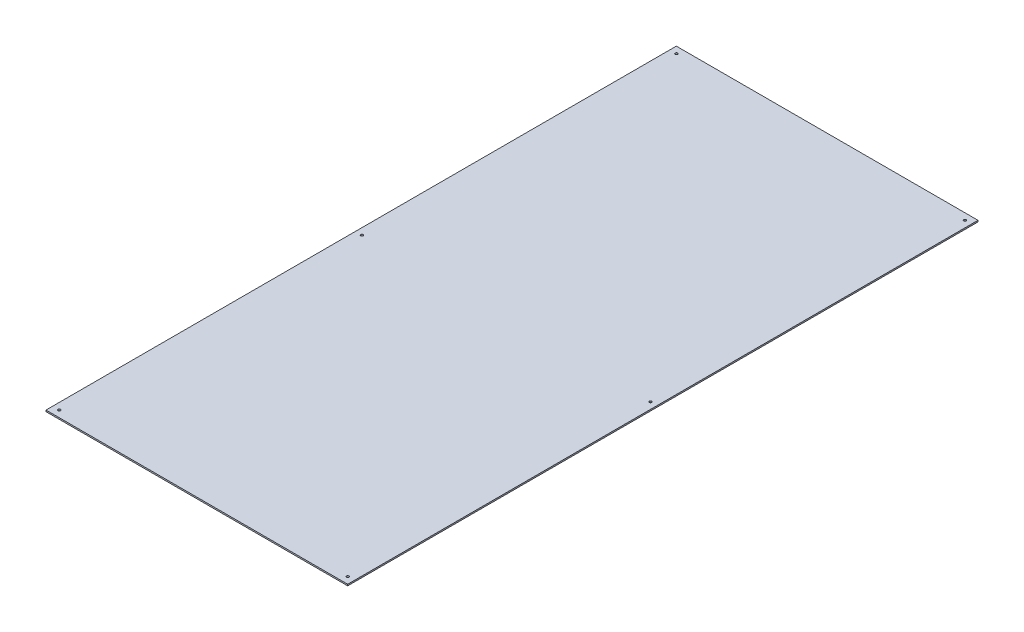
SolidWorks part; units mm, degrees
ref_plane "Front Plane" through (0, 0, 0) normal (0, 0, 1) x (1, 0, 0)
ref_plane "Top Plane" through (0, 0, 0) normal (0, 1, 0) x (1, 0, 0)
ref_plane "Right Plane" through (0, 0, 0) normal (1, 0, 0) x (0, 0, -1)
sketch "Sketch1" plane through (0, 0, 0) normal (0, 1, 0) x (1, 0, 0)
  line L0 (278.3, 595.3125) -> (278.3, -595.3125) construction
  line L1 (291, 608.0125) -> (-291, 608.0125)
  line L2 (291, 608.0125) -> (291, -608.0125)
  line L3 (291, -608.0125) -> (-291, -608.0125)
  line L4 (-291, 608.0125) -> (-291, -608.0125)
  line L5 (291, 608.0125) -> (-291, -608.0125) construction
  line L6 (291, -608.0125) -> (-291, 608.0125) construction
  line L7 (278.3, -595.3125) -> (-278.3, -595.3125) construction
  line L8 (-278.3, 595.3125) -> (-278.3, -595.3125) construction
  line L9 (278.3, 595.3125) -> (-278.3, 595.3125) construction
  circle A0 centre (278.3, 595.3125) radius 2.3813
  circle A1 centre (-278.3, 595.3125) radius 2.3813
  circle A2 centre (-278.3, -11.1125) radius 2.3813
  circle A3 centre (278.3, -11.1125) radius 2.3813
  circle A4 centre (-278.3, -595.3125) radius 2.3813
  circle A5 centre (278.3, -595.3125) radius 2.3813
  point P0 (0, 0)
  point P18 (0, 0)
  point P19 (278.3, 21.0151)
  point P20 (0, 0)
  point P21 (-278.3, 26.8316)
  dimension "D4" = 4.7625
  dimension "D1" = 1216.025
  dimension "D2" = 582
  dimension "D5" = 619.125
  dimension "D3" = 12.7
extrude "Boss-Extrude1" add sketch "Sketch1" along normal blind 2.8
